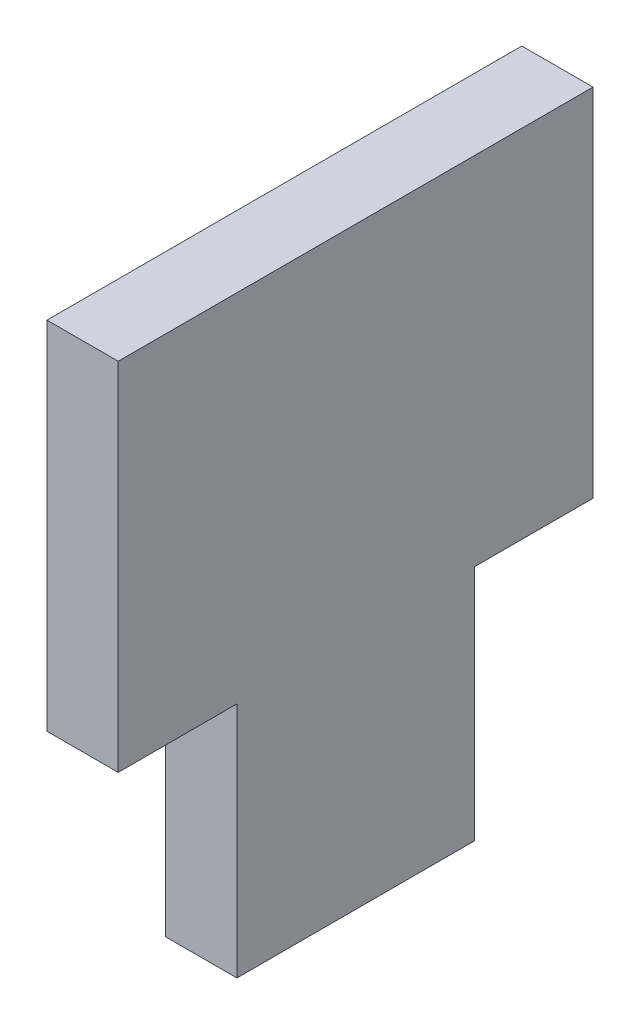
SolidWorks part; units mm, degrees
ref_plane "Front Plane" through (0, 0, 0) normal (0, 0, 1) x (1, 0, 0)
ref_plane "Top Plane" through (0, 0, 0) normal (0, 1, 0) x (1, 0, 0)
ref_plane "Right Plane" through (0, 0, 0) normal (1, 0, 0) x (0, 0, -1)
sketch "Sketch1" plane through (0, 0, 0) normal (1, 0, 0) x (0, 0, -1)
  line L0 (-5, -7.5) -> (-5, -17.5)
  line L1 (-10, -7.5) -> (-5, -7.5)
  line L2 (-10, -7.5) -> (-10, 7.5)
  line L3 (-10, 7.5) -> (10, 7.5)
  line L4 (10, -7.5) -> (10, 7.5)
  line L5 (-10, -7.5) -> (10, 7.5) construction
  line L6 (-10, 7.5) -> (10, -7.5) construction
  line L7 (-5, -17.5) -> (5, -17.5)
  line L8 (5, -17.5) -> (5, -7.5)
  line L9 (5, -7.5) -> (10, -7.5)
  point P0 (0, 0)
  dimension "D1" = 20
  dimension "D2" = 15
  dimension "D3" = 10
  dimension "D4" = 10
  dimension "D5" = 5
extrude "Boss-Extrude1" add sketch "Sketch1" along normal blind 3
